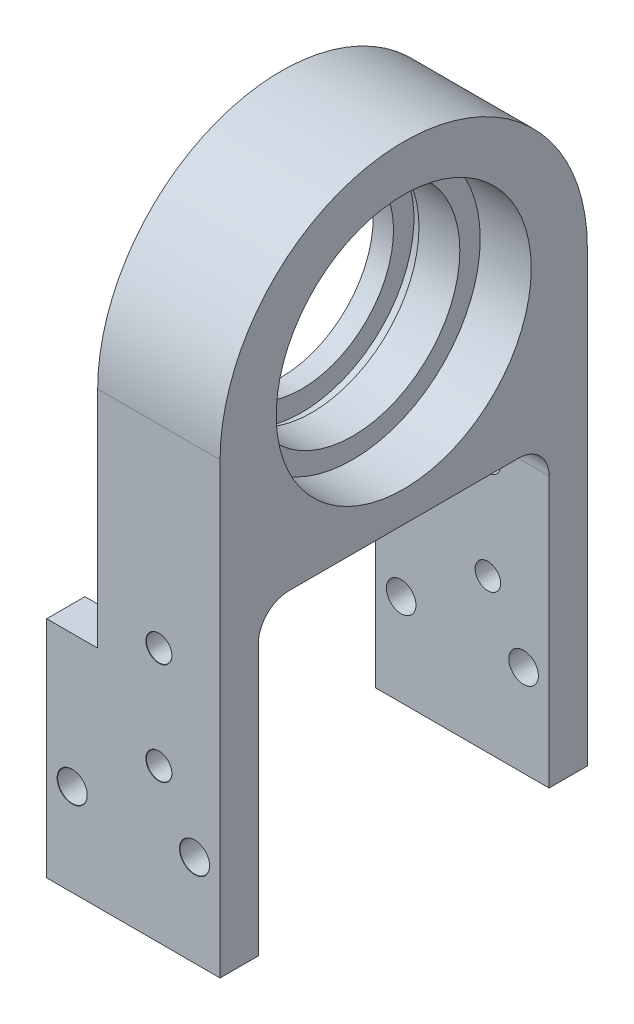
SolidWorks part; units mm, degrees
material "6061 Alloy"
ref_plane "Front Plane" through (0, 0, 0) normal (0, 0, 1) x (1, 0, 0)
ref_plane "Top Plane" through (0, 0, 0) normal (0, 1, 0) x (1, 0, 0)
ref_plane "Right Plane" through (0, 0, 0) normal (1, 0, 0) x (0, 0, -1)
sketch "Sketch1" plane through (0, 0, 0) normal (0, 0, 1) x (1, 0, 0)
  line L0 (0, 0) -> (17, 0)
  line L1 (17, 0) -> (17, 29)
  line L3 (17, 29) -> (17, 62)
  line L4 (17, 62) -> (5, 62)
  line L5 (5, 62) -> (5, 22)
  line L6 (5, 22) -> (0, 22)
  line L7 (0, 22) -> (0, 0)
  dimension "D1" = 17
  dimension "D2" = 62
  dimension "D3" = 22
  dimension "D4" = 12
extrude "Boss-Extrude1" add sketch "Sketch1" along normal blind 36
sketch "Sketch2" plane through (17, 0, 0) normal (1, 0, 0) x (0, 0, -1)
  line L0 (-18, 62) -> (-18, 12.1467) construction
  line L1 (-36, 62) -> (0, 62) construction
  circle A0 centre (-18, 45) radius 10.5
  dimension "D1" = 21
  dimension "D2" = 17
extrude "Cut-Extrude1" cut sketch "Sketch2" against normal through all
sketch "Sketch3" plane through (17, 0, 0) normal (1, 0, 0) x (0, 0, -1)
  line L0 (-36, 0) -> (0, 0) construction
  line L1 (-32.25, 0) -> (-3.75, 0)
  line L2 (-32.25, 0) -> (-32.25, 29.5)
  line L3 (-32.25, 29.5) -> (-3.75, 29.5)
  line L4 (-3.75, 0) -> (-3.75, 29.5)
  line L6 (-18, 0) -> (-18, 45) construction
  dimension "D1" = 28.5
  dimension "D2" = 29.5
extrude "Cut-Extrude2" cut sketch "Sketch3" against normal through all
sketch "Sketch6" plane through (5, 0, 0) normal (-1, 0, 0) x (0, 0, 1)
  circle A0 centre (18, 45) radius 10.5 construction
  circle A1 centre (18, 45) radius 10.5
  circle A2 centre (18, 45) radius 9
  dimension "D1" = 1.5
extrude "Boss-Extrude2" add sketch "Sketch6" against normal blind 2
sketch "Sketch10" plane through (5, 0, 0) normal (-1, 0, 0) x (0, 0, 1)
  circle A0 centre (18, 45) radius 11
  circle A1 centre (18, 45) radius 15
  dimension "D1" = 22
  dimension "D2" = 30
extrude "Cut-Extrude4" cut sketch "Sketch10" against normal blind 0.6
sketch "Sketch11" plane through (17, 0, 0) normal (1, 0, 0) x (0, 0, -1)
  circle A0 centre (-18, 45) radius 12.5
  dimension "D1" = 25
extrude "Cut-Extrude5" cut sketch "Sketch11" against normal blind 5
sketch "Sketch14" plane through (0, 0, 36) normal (0, 0, 1) x (1, 0, 0)
  line L0 (2.5, 9) -> (14.5, 9)
  line L3 (8.5, 9) -> (8.5, 0)
  line L4 (0, 0) -> (17, 0) construction
  line L6 (17, 32.5) -> (17, 57.5) construction
  line L7 (17, 32.5) -> (17, 57.5) construction
  point P0 (14.5, 9)
  point P2 (2.5, 9)
  point P25 (17, 45)
  dimension "D1" = 36
  dimension "D2" = 12
hole_wizard "M2.5 Clearance Hole1" positions "Sketch14" profile "Sketch13" hole size "M2.5" standard "DIN" end condition through all
sketch "Sketch13" plane through (14.5, 9, 36) normal (1, 0, 0) x (0, -1, 0)
  line L0 (0, 0) -> (0, 36)
  line L1 (0, 36) -> (1.45, 36)
  line L2 (1.45, 36) -> (1.45, 0.025)
  line L3 (1.45, 0.025) -> (1.475, 0)
  line L5 (1.475, 0) -> (0, 0)
  line L6 (-1.45, 0.025) -> (-1.475, 0) construction
  line L11 (0, -6.35) -> (0, 107.95) construction
  dimension "Thru Hole Dia." = 2.9
  dimension "Thru Hole Depth" = 36
  dimension "Near C'Sink Dia." = 2.95
  dimension "Near C'Sink Angle" = 90
sketch "Sketch15" plane through (0, 0, 0) normal (0, 0, -1) x (-1, 0, 0)
  line L0 (-14.5, 9) -> (-14.5, 3) construction
  line L1 (-13.05, 9) -> (-13.05, 3)
  line L2 (-15.95, 9) -> (-15.95, 3)
  line L3 (-2.5, 9) -> (-2.5, 3) construction
  line L4 (-1.05, 9) -> (-1.05, 3)
  line L5 (-3.95, 9) -> (-3.95, 3)
  arc A0 (-13.05, 9) -> (-15.95, 9) centre (-14.5, 9) ccw
  arc A1 (-15.95, 3) -> (-13.05, 3) centre (-14.5, 3) ccw
  arc A2 (-1.05, 9) -> (-3.95, 9) centre (-2.5, 9) ccw
  arc A3 (-3.95, 3) -> (-1.05, 3) centre (-2.5, 3) ccw
  circle A4 centre (-14.5, 9) radius 1.45 construction
  point P3 (-14.5, 6)
  point P8 (-2.5, 6)
  dimension "D1" = 6
extrude "Cut-Extrude6" [suppressed] cut sketch "Sketch15" against normal through all
sketch "Sketch16" plane through (0, 0, 0) normal (0, 0, -1) x (-1, 0, 0)
  line L0 (0, 22) -> (-5, 32)
  line L1 (-5, 62) -> (-5, 22) construction
  dimension "D1" = 10
rib "Rib6" [suppressed] sketch "Sketch16" sketch "Sketch16" thickness 3.75 extrusion direction parallel to sketch draft on no parameters "D1"=3.75
sketch "Sketch17" plane through (17, 0, 0) normal (1, 0, 0) x (0, 0, -1)
  line L1 (-36, 62) -> (0, 62)
  line L2 (-36, 62) -> (-36, 45)
  line L3 (-36, 45) -> (0, 45)
  line L4 (0, 62) -> (0, 45)
  circle A0 centre (-18, 45) radius 18
  line M9 (0, 0) -> (0, 62)
  line M10 (0, 62) -> (-36, 62)
  line M11 (-36, 62) -> (-36, 0)
extrude "Cut-Extrude7" cut sketch "Sketch17" against normal through all contours A0 M10 M11 | A0 M9 M10 region at (17, 58.082, 32.7544) region at (17, 58.082, 3.2456)
sketch "Sketch18" plane through (7, 0, 0) normal (1, 0, 0) x (0, 0, -1)
  circle A0 centre (-18, 45) radius 9 construction
  circle A1 centre (-18, 45) radius 9
  circle A2 centre (-18, 45) radius 9.4
  dimension "D1" = 0.4
extrude "Boss-Extrude3" [suppressed] add sketch "Sketch18" along normal up to surface (10 mm away) up to face at (17, 45, 5.5)
sketch "Sketch19" plane through (12, 0, 0) normal (1, 0, 0) x (0, 0, -1)
  circle A0 centre (-18, 45) radius 10.5 construction
  circle A1 centre (-18, 45) radius 10.5
  circle A2 centre (-18, 45) radius 10.9
  dimension "D1" = 0.4
extrude "Boss-Extrude4" [suppressed] add sketch "Sketch19" along normal up to surface (5 mm away) up to face at (17, 45, 5.5)
sketch "Sketch22" plane through (0, 0, 36) normal (0, 0, 1) x (1, 0, 0)
  line L0 (11, 45) -> (11, -8.6789) construction
  line L1 (5, 45) -> (17, 45) construction
  line L2 (0, 0) -> (17, 0) construction
  point P7 (11, 25)
  point P9 (11, 15)
  dimension "D1" = 10
  dimension "D2" = 15
hole_wizard "Tap Drill for M3 Tap1" positions "Sketch22" profile "Sketch21" hole size "M3" standard "DIN" end condition through all
sketch "Sketch21" plane through (11, 15, 36) normal (1, 0, 0) x (0, -1, 0)
  line L0 (0, 0) -> (0, 36)
  line L1 (0, 36) -> (1.25, 36)
  line L2 (1.25, 36) -> (1.25, 0.025)
  line L3 (1.25, 0.025) -> (1.275, 0)
  line L5 (1.275, 0) -> (0, 0)
  line L6 (-1.25, 0.025) -> (-1.275, 0) construction
  line L11 (0, -6.35) -> (0, 107.95) construction
  dimension "Thru Hole Dia." = 2.5
  dimension "Thru Hole Depth" = 36
  dimension "Near C'Sink Dia." = 2.55
  dimension "Near C'Sink Angle" = 90
sketch "Sketch23" plane through (17, 0, 0) normal (1, 0, 0) x (0, 0, -1)
  line L0 (-36, 0) -> (-36, 45) construction
  line L1 (0, 0) -> (0, 45) construction
  line L2 (-23.9161, 62) -> (-12.0839, 62) construction
  line L13 (-36, 45) -> (-36, 0)
  line L14 (-36, 0) -> (-32.25, 0)
  line L15 (-32.25, 0) -> (-32.25, 29.5)
  line L17 (-32.25, 29.5) -> (-3.75, 29.5)
  line L19 (-3.75, 29.5) -> (-3.75, 0)
  line L20 (-3.75, 0) -> (0, 0)
  line L21 (0, 0) -> (0, 45)
  line L22 (-12.0839, 62) -> (-23.9161, 62)
  line L23 (-36, 45) -> (-36, 0)
  line L24 (-36, 0) -> (-32.25, 0)
  line L25 (-32.25, 0) -> (-32.25, 29.5)
  line L27 (-32.25, 29.5) -> (-3.75, 29.5)
  line L29 (-3.75, 29.5) -> (-3.75, 0)
  line L30 (-3.75, 0) -> (0, 0)
  line L31 (0, 0) -> (0, 45)
  line L32 (-12.0839, 62) -> (-23.9161, 62)
  circle A0 centre (-18, 44) radius 18
  arc A3 (-23.9161, 62) -> (-36, 45) centre (-18, 45) ccw
  arc A4 (0, 45) -> (-12.0839, 62) centre (-18, 45) ccw
  arc A5 (-23.9161, 62) -> (-36, 45) centre (-18, 45) ccw
  arc A6 (0, 45) -> (-12.0839, 62) centre (-18, 45) ccw
  arc M15 (-23.9161, 62) -> (-36, 45) centre (-18, 45) ccw
  line M16 (-36, 45) -> (-36, 0)
  arc M25 (0, 45) -> (-12.0839, 62) centre (-18, 45) ccw
  line M26 (-12.0839, 62) -> (-23.9161, 62)
  dimension "D1" = 0
extrude "Cut-Extrude8" cut sketch "Sketch23" against normal through all contours A0 L32 M15 M16 | A0 L31 M25 M26 region at (17, 55.2811, 32.4637) region at (17, 61.9745, 15.042)
sketch "Sketch24" plane through (5, 0, 0) normal (-1, 0, 0) x (0, 0, 1)
  line L0 (3.75, 29.5) -> (32.25, 29.5) construction
  line L1 (13, 29.5) -> (23, 29.5)
  line L2 (13, 29.5) -> (13, 30.8579)
  line L3 (13, 30.8579) -> (23, 30.8579)
  line L4 (23, 29.5) -> (23, 30.8579)
  circle A0 centre (18, 45) radius 15 construction
  point P8 (0, 0)
  dimension "D1" = 10
extrude "Cut-Extrude10" cut sketch "Sketch24" against normal up to surface (0.6 mm away) up to face at (5.6, 34, 18)
fillet "Fillet1" radius 4 2 edges at (5.3, 30.8579, 23) (5.3, 30.8579, 13)
fillet "Fillet2" radius 3 2 edges at (11, 29.5, 32.25) (11, 29.5, 3.75)
ref_plane "Plane1" through (0, 0, 18) normal (0, 0, -1) x (-1, 0, 0)
sketch "Sketch25" plane through (0, 0, 18) normal (0, 0, -1) x (-1, 0, 0)
  line L0 (-7, 34.5) -> (-7, 34)
  line L1 (-7, 55.5) -> (-7, 34.5) construction
  line L2 (-7, 34) -> (-8, 34)
  line L3 (-8, 34) -> (-8, 34.5)
  line L4 (-8, 34.5) -> (-7, 34.5)
  line L5 (-5, 45) -> (-19.1096, 45) construction
  line L6 (-5, 36) -> (-5, 54) construction
  dimension "D1" = 1
  dimension "D2" = 0.5
revolve "Cut-Revolve1" cut sketch "Sketch25" angle 360 about L5
